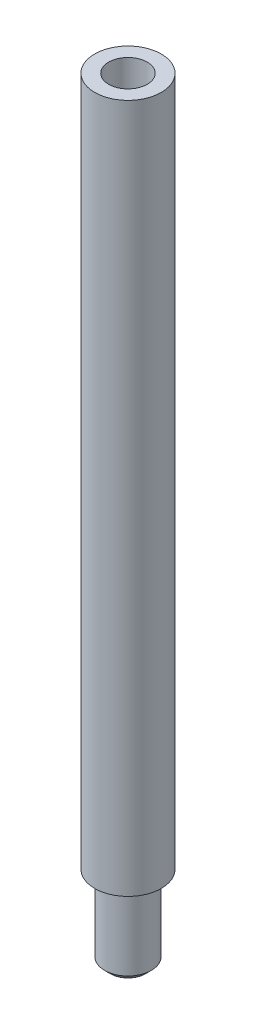
SolidWorks part; units mm, degrees
ref_plane "Front Plane" through (0, 0, 0) normal (0, 0, 1) x (1, 0, 0)
ref_plane "Top Plane" through (0, 0, 0) normal (0, 1, 0) x (1, 0, 0)
ref_plane "Right Plane" through (0, 0, 0) normal (1, 0, 0) x (0, 0, -1)
sketch "Sketch1" plane through (0, 0, 0) normal (0, 1, 0) x (1, 0, 0)
  circle A0 centre (0, 0) radius 2.85
  circle A1 centre (0, 0) radius 2
extrude "Boss-Extrude1" add sketch "Sketch1" along normal blind 59 contours A1 | A0 A1 region at (-2.7694, 0, 0) region at (0, 0, 0)
extrude "Boss-Extrude2" add sketch "Sketch1<4>" against normal blind 7 contours A1 region at (0, 0, 0)
sketch "Sketch1<4>" plane through (0, 0, 0) normal (0, 1, 0) x (1, 0, 0) same geometry as "Sketch1"
hole_wizard "M4x0.7 Tapped Hole1" positions "Sketch2" profile "Sketch3" tap size "M4x0.7" standard "ANSI Metric"
sketch "Sketch2" plane through (0, 59, 0) normal (0, 1, 0) x (1, 0, 0)
  point P0 (0, 0)
cosmetic thread "Hole Thread1" parameters "D1"=8, "D2"=4
sketch "Sketch3" plane through (0, 59, 0) normal (1, 0, 0) x (0, 0, 1)
  line L0 (0, 0) -> (0, 11.0914)
  line L1 (0, 11.0914) -> (1.65, 10.1)
  line L2 (1.65, 10.1) -> (1.65, 0)
  line L5 (1.65, 0) -> (0, 0)
  line L10 (0, 11.0914) -> (-1.65, 10.1) construction
  line L11 (0, -6.35) -> (0, 107.95) construction
  dimension "Tap Drill Dia." = 3.3
  dimension "Tap Drill Depth" = 10.1
  dimension "Drill Angle" = 118
chamfer "Chamfer1" distance 0.5 angle 45 1 edges at (0, -7, 2)
